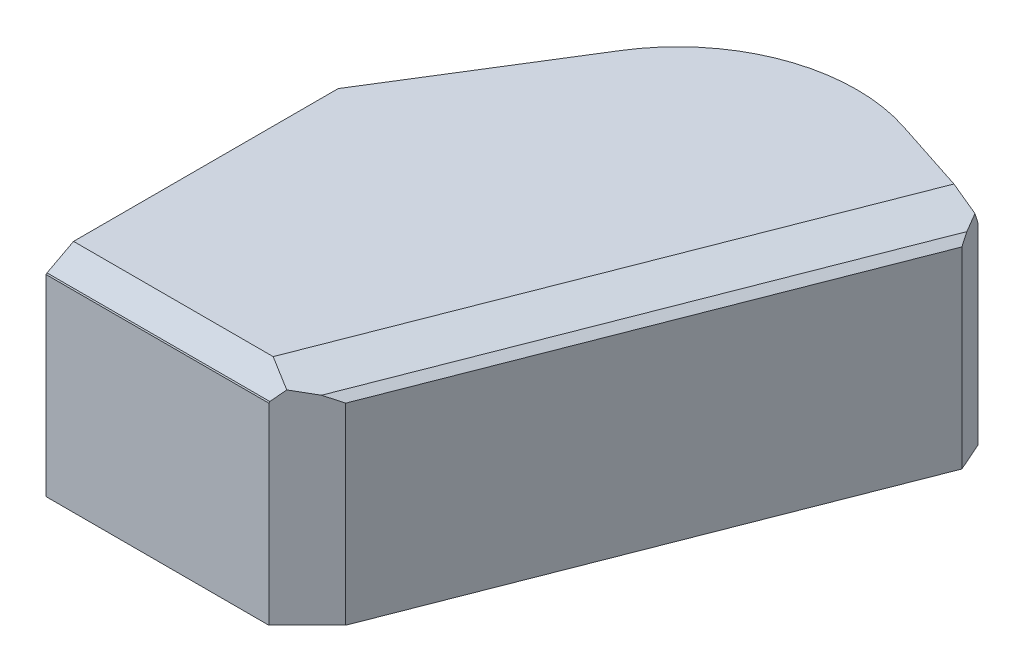
SolidWorks part; units mm, degrees
material "Nickel"
ref_plane "Front Plane" through (0, 0, 0) normal (0, 0, 1) x (1, 0, 0)
ref_plane "Top Plane" through (0, 0, 0) normal (0, 1, 0) x (1, 0, 0)
ref_plane "Right Plane" through (0, 0, 0) normal (1, 0, 0) x (0, 0, -1)
sketch "Sketch1" plane through (0, 0, 0) normal (0, 1, 0) x (1, 0, 0)
  line L0 (-66.6738, 0) -> (-37.0678, 47.6333)
  line L1 (0, 0) -> (-66.6738, 0) construction
  line L2 (0, 0) -> (0, -77.4519) construction
  line L3 (0, -77.4519) -> (-66.6738, -77.4519)
  line L4 (-66.6738, 0) -> (-66.6738, -77.4519)
  line L5 (21.8265, 69.1139) -> (53.1385, 58.9035)
  line L6 (53.1385, 58.9035) -> (0, -77.4519)
  arc A0 (-37.0678, 47.6333) -> (21.8265, 69.1139) centre (6.0775, 20.8169) cw
  point P5 (-16.0418, 81.4623)
  dimension "D1" = 50.8
extrude "Boss-Extrude1" add sketch "Sketch1" along normal blind 58.42
chamfer "Chamfer1" distance 6.35 angle 45 3 edges at (0, 29.21, 77.4519) (26.5692, 58.42, 9.2742) (53.1385, 29.21, -58.9035)
chamfer "Chamfer2" distance 6.35 angle 20 1 edges at (-36.7445, 58.42, 77.4519)
chamfer "Chamfer3" distance 6.35 angle 20 6 edges at (20.5886, 58.42, 7.1327) (-36.2941, 58.42, 75.1406) (34.4591, 58.42, -64.9946) (-11.3292, 58.42, -68.5416) (-51.8708, 58.42, -23.8167) (-66.6738, 58.42, 37.5703)
